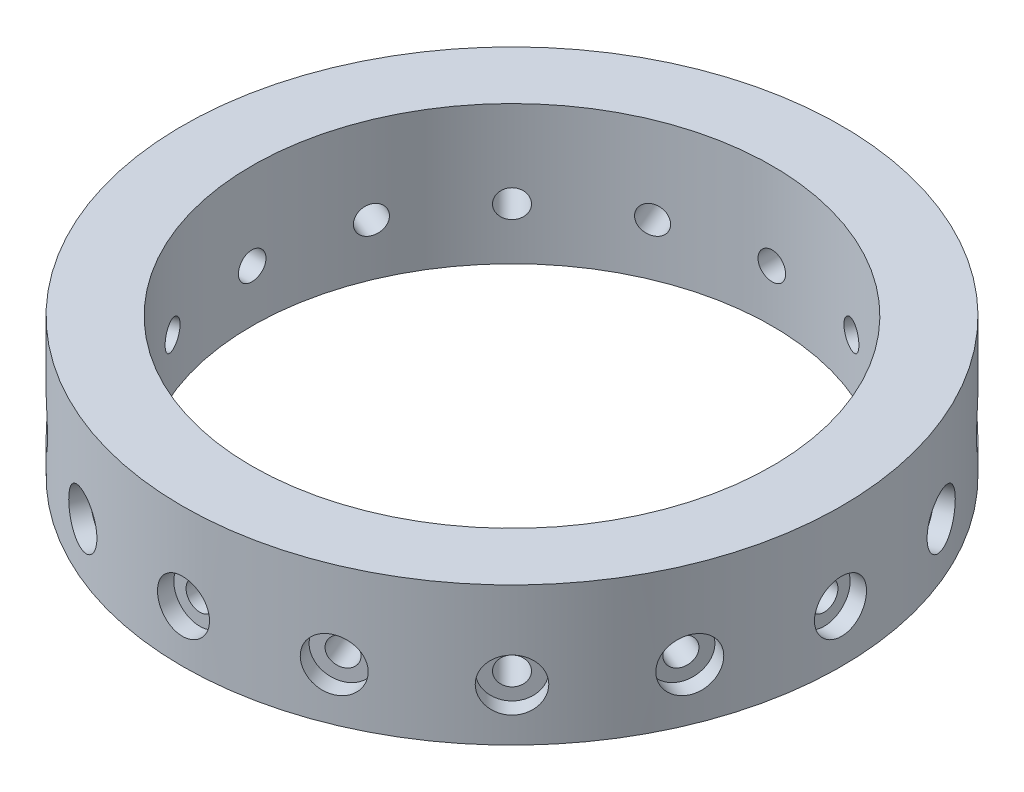
SolidWorks part; units mm, degrees
material "6061-T6 (SS)"
ref_plane "Front Plane" through (0, 0, 0) normal (0, 0, 1) x (1, 0, 0)
ref_plane "Top Plane" through (0, 0, 0) normal (0, 1, 0) x (1, 0, 0)
ref_plane "Right Plane" through (0, 0, 0) normal (1, 0, 0) x (0, 0, -1)
sketch "Sketch1" plane through (0, 0, 0) normal (0, 1, 0) x (1, 0, 0)
  circle A0 centre (0, 0) radius 60.325
  circle A1 centre (0, 0) radius 47.625
extrude "Boss-Extrude1" add sketch "Sketch1" along normal blind 25.4
ref_plane "Plane1" through (0, 0, -60.325) normal (0, 0, -1) x (-1, 0, 0)
sketch "Sketch2" plane through (0, 0, -60.325) normal (0, 0, -1) x (-1, 0, 0)
  line L0 (0, 0) -> (0, 9.525)
  point P4 (0, 9.525)
hole_wizard "CBORE for 1/4 Socket Head Cap Screw1" positions "Sketch3" profile "Sketch4" counterbore size "1/4" standard "ANSI Inch" end condition through all
sketch "Sketch3" plane through (0, 0, -60.325) normal (0, 0, -1) x (-1, 0, 0)
  point P0 (0, 9.525)
sketch "Sketch4" plane through (0, 9.525, -60.325) normal (1, 0, 0) x (0, 1, 0)
  line L0 (0, 0) -> (0, 120.65)
  line L1 (0, 120.65) -> (2.5273, 120.65)
  line L3 (2.5273, 120.65) -> (2.5273, 3.175)
  line L4 (2.5273, 3.175) -> (4.7625, 3.175)
  line L5 (4.7625, 3.175) -> (4.7625, 0)
  line L7 (4.7625, 0) -> (0, 0)
  line L11 (0, -6.35) -> (0, 107.95) construction
  dimension "Thru Hole Dia." = 5.0546
  dimension "Thru Hole Depth" = 120.65
  dimension "C'Bore Dia." = 9.525
  dimension "C'Bore Depth" = 3.175
sketch "Sketch5" plane through (0, 0, 0) normal (0, 0, 1) x (1, 0, 0)
  line L0 (0, 0) -> (0, 24.4952)
pattern_circular "CirPattern1" count 16 over 360 about axis through (0, 0, 0) along (0, 1, 0) of "CBORE for 1/4 Socket Head Cap Screw1" reverse direction yes
ref_plane "Plane2" through (0, 9.525, 0) normal (0, 1, 0) x (1, 0, 0)
